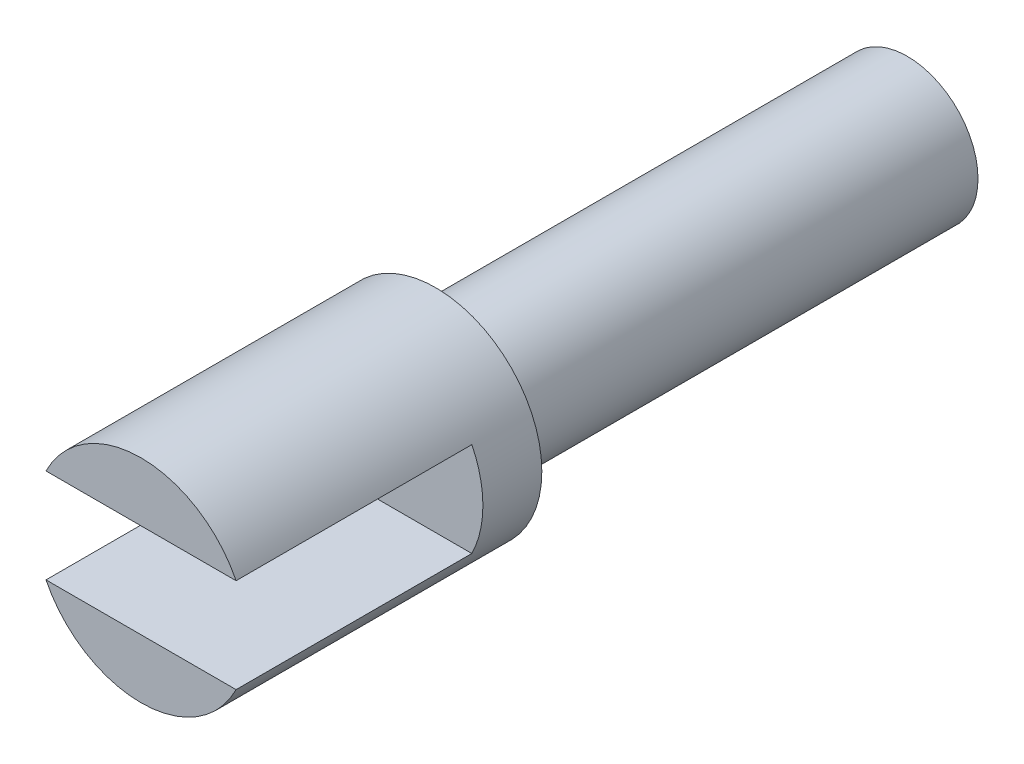
SolidWorks part; units mm, degrees
material "1.0545 (S355N)"
ref_plane "Płaszczyzna przednia" through (0, 0, 0) normal (0, 0, 1) x (1, 0, 0)
ref_plane "Płaszczyzna górna" through (0, 0, 0) normal (0, 1, 0) x (1, 0, 0)
ref_plane "Płaszczyzna prawa" through (0, 0, 0) normal (1, 0, 0) x (0, 0, -1)
sketch "Szkic1" plane through (0, 0, 0) normal (0, 1, 0) x (1, 0, 0)
  line L0 (0, -44.41) -> (0, 49.6533) construction
  line L1 (-9, 0) -> (9, 0)
  line L2 (-9, 0) -> (-9, -25)
  line L3 (-9, -25) -> (9, -25)
  line L4 (9, 0) -> (9, -25)
  line L5 (-6, 40) -> (6, 40)
  line L6 (-6, 40) -> (-6, 0)
  line L7 (-6, 0) -> (6, 0)
  line L8 (6, 40) -> (6, 0)
  point P8 (0, 0)
  point P9 (0, 0)
  dimension "D1" = 12
  dimension "D2" = 18
  dimension "D3" = 40
  dimension "D4" = 25
revolve "Obrót1" add sketch "Szkic1" angle 360 about L0 region at (4.5, 0, 12.5) region at (3, 0, -20)
sketch "Szkic2" plane through (0, 0, 25) normal (0, 0, 1) x (1, 0, 0)
  line L1 (-9, 4) -> (9, 4)
  line L2 (-9, 4) -> (-9, -4)
  line L3 (-9, -4) -> (9, -4)
  line L4 (9, 4) -> (9, -4)
  circle A2 centre (0, 0) radius 9 construction
  point P4 (0, 4)
  point P6 (-9, 0)
  point P7 (9, 0)
  dimension "D1" = 8
extrude "Wytnij-wyciągnięcie1" cut sketch "Szkic2" against normal blind 20
equation "\"D1@Wytnij-wyciągnięcie1\"=\"D4@Szkic1\" - 5"
